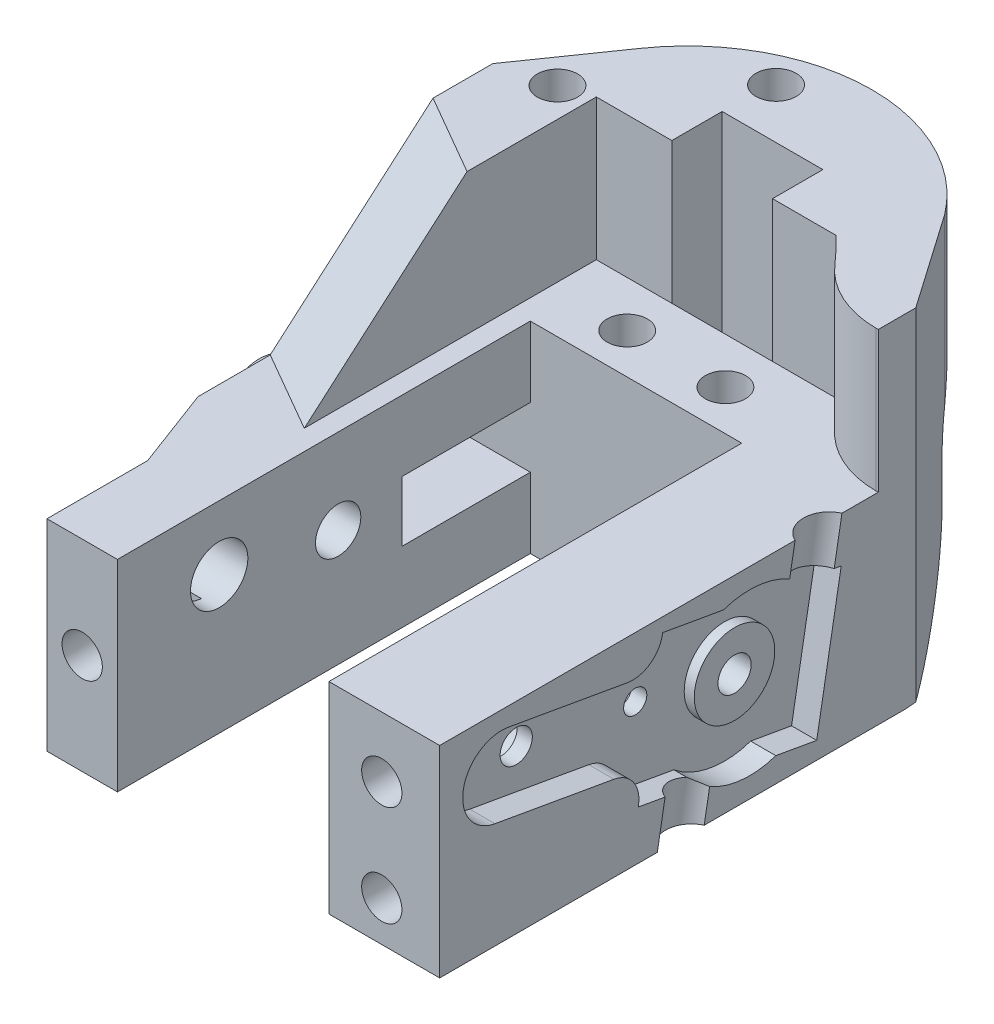
SolidWorks part; units mm, degrees
material "ABS"
ref_plane "Front Plane" through (0, 0, 0) normal (0, 0, 1) x (1, 0, 0)
ref_plane "Top Plane" through (0, 0, 0) normal (0, 1, 0) x (1, 0, 0)
ref_plane "Right Plane" through (0, 0, 0) normal (1, 0, 0) x (0, 0, -1)
sketch "Sketch1" plane through (0, 0, 0) normal (0, 1, 0) x (1, 0, 0)
  line L0 (-15.5, -37) -> (-10, -37)
  line L2 (-15.5, -37) -> (-15.5, 10)
  line L3 (-15.5, 10) -> (21, 10)
  line L4 (21, -19) -> (21, 10)
  line L5 (-10, -37) -> (-10, 4)
  line L6 (-10, 4) -> (11, 4)
  line L7 (11, 4) -> (11, -37)
  line L9 (21, -19) -> (18, -27)
  line L10 (18, -27) -> (18, -37)
  line L11 (11, -37) -> (18, -37)
  point P0 (0, 0)
  dimension "D1" = 36.5
  dimension "D2" = 7
  dimension "D3" = 21
  dimension "D4" = 10
  dimension "D5" = 21
  dimension "D6" = 41
  dimension "D7" = 47
  dimension "D8" = 8
  dimension "D9" = 5.5
  dimension "D10" = 10
extrude "Boss-Extrude1" add sketch "Sketch1" along normal blind 20
sketch "Sketch6" plane through (-15.5, 0, 0) normal (-1, 0, 0) x (0, 0, 1)
  line L1 (15, 0) -> (-10, 0)
  line L2 (15, 0) -> (15, 20)
  line L3 (15, 20) -> (-10, 20)
  line L4 (-10, 0) -> (-10, 20)
  line L5 (-10, 20) -> (-10, 0) construction
  line L7 (-10, 0) -> (37, 0) construction
  line L8 (-10, 20) -> (37, 20) construction
  dimension "D3" = 25
extrude "Boss-Extrude5" add sketch "Sketch6" along normal blind 5.5
sketch "Sketch20" plane through (0, 20, 0) normal (0, 1, 0) x (1, 0, 0)
  line L4 (-21, 6.5542) -> (13, 6.5542)
  line L11 (21.0063, -11.8234) -> (21.0063, 10.2821)
  line L12 (21.0063, 10.2821) -> (15.0032, 18.9016)
  line L13 (15.0032, 18.9016) -> (-14.9968, 18.9016)
  line L14 (-14.9968, 18.9016) -> (-21, 10.2821)
  line L15 (-21, 10) -> (-21, -15) construction
  line L16 (-21, 10.2821) -> (-21, 6.5542)
  line L18 (13, 6.5542) -> (13, -16.4458)
  line L20 (13, -16.4458) -> (21.0063, -11.8234)
  dimension "D2" = 23
  dimension "D4" = 30
  dimension "D8" = 34
  dimension "D9" = 60
  dimension "D1" = 6.0032
  dimension "D3" = 6.0032
  dimension "D5" = 8.6195
  dimension "D6" = 8.6195
  dimension "D7" = 3.7279
extrude "Boss-Extrude11" add sketch "Sketch20" along normal blind 14 and the other way up to surface (20 mm away) other way up to face at (0.5833, 0, 16.3333)
sketch "Sketch4" plane through (0, 20, 0) normal (0, 1, 0) x (1, 0, 0)
  line L2 (-10, 4) -> (11, 4) construction
  line L4 (-10, -37) -> (-10, 4) construction
  circle A6 centre (-4.375, 8) radius 2
  circle A7 centre (5.375, 8) radius 2
  dimension "D1" = 4
  dimension "D2" = 4
  dimension "D3" = 9.75
  dimension "D4" = 5.625
extrude "Cut-Extrude1" cut sketch "Sketch4" against normal blind 10
sketch "Sketch24" plane through (0, 34, 0) normal (0, 1, 0) x (1, 0, 0)
  line L0 (21.0063, 10.2821) -> (15.0032, 18.9016) construction
  line L1 (-14.9968, 18.9016) -> (-14.4209, 19.7285)
  line L2 (-21, 10.2821) -> (-21, 6.5542) construction
  line L3 (-14.9968, 18.9016) -> (-21, 10.2821) construction
  line L4 (21.0063, 10.2821) -> (15.0032, 18.9016)
  line L6 (-21, 10.2821) -> (-21, 6.5542)
  line L7 (-14.9968, 18.9016) -> (-21, 10.2821)
  line L11 (-21, 6.5542) -> (13, 6.5542) construction
  line L14 (-21, 6.5542) -> (21.0063, 6.5542)
  line L16 (21.0063, 10.2821) -> (21.0063, 6.5542)
  line L17 (21.0063, -11.8234) -> (21.0063, 10.2821) construction
  arc A3 (8.6131, 24.6437) -> (-14.4209, 19.7285) centre (-0.0555, 8.8374) ccw
  arc A4 (8.6131, 24.6437) -> (15.0032, 18.9016) centre (-0.4313, 8.152) cw
  dimension "D3" = 18.0273
  dimension "D4" = 18.8089
  dimension "D1" = 0.5759
  dimension "D2" = 1.0077
extrude "Boss-Extrude13" add sketch "Sketch24" against normal blind 12
fillet "Fillet11" radius 7.95 1 edges at (0.0032, 22, -18.9016)
chamfer "Chamfer1" distance 14 angle 45 1 edges at (17.0032, 34, 14.1346)
sketch "Sketch26" plane through (-21, 0, 0) normal (-1, 0, 0) x (0, 0, 1)
  line L0 (15, 0) -> (37, 0)
  line L2 (37, 0) -> (37, 20)
  line L3 (37, 20) -> (15, 20)
  line L4 (15, 0) -> (15, 20) construction
  line L5 (15, 20) -> (15, 0)
extrude "Boss-Extrude14" add sketch "Sketch26" against normal up to surface (11 mm away) up to face at (-10, 10, 16.5)
sketch "Sketch25" plane through (-21, 0, 0) normal (-1, 0, 0) x (0, 0, 1)
  line L0 (12.4376, 15.0315) -> (30.1652, 18.1573)
  line L1 (13.7834, 7.3992) -> (31.511, 10.5251)
  line L2 (31.511, 10.5251) -> (30.1652, 18.1573) construction
  line L3 (6.2179, 10) -> (30.8381, 14.3412) construction
  line L4 (-10.2821, 0) -> (37, 0) construction
  line L5 (6.2179, 10) -> (6.2179, 38.8588) construction
  line L7 (-10.2821, 34) -> (-10.2821, 0) construction
  arc A1 (12.4376, 15.0315) -> (13.7834, 7.3992) centre (6.2179, 10) ccw
  arc A3 (30.1652, 18.1573) -> (31.511, 10.5251) centre (30.8381, 14.3412) cw
  dimension "D1" = 8
  dimension "D2" = 7.75
  dimension "D4" = 7.75
  dimension "D3" = 25
  dimension "D5" = 80
  dimension "D7" = 10
  dimension "D6" = 16.5
extrude "Cut-Extrude7" cut sketch "Sketch25" against normal blind 2.5
sketch "Sketch27" plane through (-18.5, 0, 0) normal (-1, 0, 0) x (0, 0, 1)
  line L0 (6.2179, 10) -> (30.8381, 14.3412) construction
  circle A0 centre (6.2179, 10) radius 4
  circle A1 centre (15.0812, 11.5628) radius 1.15
  circle A4 centre (26.8989, 13.6466) radius 1.6
  dimension "D1" = 8
  dimension "D3" = 2.3
  dimension "D4" = 3.2
  dimension "D2" = 9
  dimension "D5" = 4
extrude "Cut-Extrude8" cut sketch "Sketch27" against normal up to next
sketch "Sketch28" plane through (-21, 0, 0) normal (-1, 0, 0) x (0, 0, 1)
  line L0 (-2.8761, 15.5045) -> (14.8505, 18.6301)
  line L1 (14.8505, 18.6301) -> (17.2815, 4.8428)
  line L2 (17.2815, 4.8428) -> (-0.445, 1.7172)
  line L3 (-0.445, 1.7172) -> (-2.8761, 15.5045)
  line L6 (30.1652, 18.1573) -> (12.4376, 15.0315) construction
  circle A0 centre (6.2179, 10) radius 4 construction
  dimension "D1" = 10
  dimension "D2" = 7
  dimension "D3" = 14
  dimension "D4" = 18
extrude "Cut-Extrude9" cut sketch "Sketch28" against normal blind 2.5
sketch "Sketch29" plane through (0, 15.5288, -2.7381) normal (0, -0.9848, 0.1736) x (1, 0, 0)
  line L0 (-18.5, 3.987) -> (-18.5, -0.14) construction
  line L3 (-21, 11.7329) -> (-21, 3.987) construction
  circle A0 centre (-22, 2.86) radius 2.5
  point P6 (-21, 7.86)
  dimension "D1" = 5
  dimension "D2" = 3.5
  dimension "D3" = 5
extrude "Cut-Extrude10" cut sketch "Sketch29" against normal up to next
sketch "Sketch30" plane through (0, 1.7415, -0.3071) normal (0, 0.9848, -0.1736) x (1, 0, 0)
  line L0 (-21, -11.7329) -> (-21, -17.86) construction
  line L1 (-21, -3.987) -> (-21, -11.7329) construction
  circle A0 centre (-22, -12.86) radius 2.5
  point P6 (-21, -7.86)
  dimension "D1" = 5
  dimension "D2" = 1
  dimension "D3" = 5
extrude "Cut-Extrude11" cut sketch "Sketch30" against normal up to next
sketch "Sketch31" plane through (-18.5, 0, 0) normal (-1, 0, 0) x (0, 0, 1)
  circle A0 centre (6.2179, 10) radius 4
  circle A1 centre (6.2179, 10) radius 1.65
  dimension "D1" = 8
  dimension "D2" = 3.3
extrude "Boss-Extrude15" add sketch "Sketch31" along normal blind 1 and the other way blind 2
sketch "Sketch32" plane through (-10, 0, 0) normal (1, 0, 0) x (0, 0, -1)
  circle A0 centre (-26.8989, 13.6466) radius 2.85
  circle A3 centre (-15.0812, 11.5628) radius 2.25
  dimension "D1" = 5.7
  dimension "D2" = 4.5
extrude "Cut-Extrude12" cut sketch "Sketch32" against normal blind 7 and the other way up to next
sketch "Sketch33" plane through (21.0063, 0, 0) normal (1, 0, 0) x (0, 0, -1)
  circle A0 centre (-6.2179, 10) radius 3.8
  circle A1 centre (-6.2179, 10) radius 1.65 construction
  dimension "D1" = 7.6
extrude "Boss-Extrude17" add sketch "Sketch33" along normal blind 7
fillet "Fillet17" radius 1 1 edges at (28.0063, 10, 2.4179)
sketch "Sketch35" plane through (0, 34, 0) normal (0, 1, 0) x (1, 0, 0)
  line L0 (-21, 6.5542) -> (13, 6.5542) construction
  line L1 (-20.8, 6.5542) -> (13, 6.5542)
  line L3 (-10.8027, 12.5542) -> (13, 12.5542)
  line L4 (13, 6.5542) -> (13, 12.5542)
  line L7 (13, 6.5542) -> (13, -0.28) construction
  arc A0 (-20.8, 6.5542) -> (-13.285, 9.9568) centre (-20.8, 16.5542) ccw
  arc A1 (-13.285, 9.9568) -> (-10.8027, 12.5542) centre (18.6614, -18.0889) cw
  dimension "D3" = 42.5104
  dimension "D4" = 10
  dimension "D5" = 8.2494
  dimension "D1" = 23.8027
  dimension "D2" = 6
  dimension "D6" = 9.9972
extrude "Cut-Extrude13" cut sketch "Sketch35" against normal up to surface (14 mm away) up to face at (1.4167, 20, 9.7117)
sketch "Sketch36" plane through (0, 0, 37) normal (0, 0, 1) x (1, 0, 0)
  line L0 (11, 20) -> (11, 0) construction
  line L1 (11, 20) -> (18, 20) construction
  line L2 (-21, 0) -> (-21, 20) construction
  line L6 (-21, 20) -> (-10, 20) construction
  circle A0 centre (-15.25, 14) radius 2
  circle A1 centre (14.5, 10) radius 2
  circle A2 centre (-15.25, 4) radius 2
  dimension "D3" = 4
  dimension "D1" = 5.75
  dimension "D2" = 3.5
  dimension "D4" = 10
  dimension "D5" = 6
  dimension "D6" = 5.75
  dimension "D7" = 10
extrude "Cut-Extrude14" cut sketch "Sketch36" against normal blind 10
fillet "Fillet18" radius 10 1 edges at (0.0032, 0, -18.9016)
sketch "Sketch37" plane through (21, 0, 0) normal (1, 0, 0) x (0, 0, -1)
  line L0 (-6.2179, 10) -> (6.304, 10) construction
  line L1 (4, 20) -> (4, 0) construction
  line L2 (-1.7179, 13) -> (4, 13)
  line L3 (-1.7179, 13) -> (-1.7179, 7)
  line L4 (-1.7179, 7) -> (4, 7)
  line L5 (4, 13) -> (4, 7)
  point P7 (0.043, 10)
  dimension "D1" = 6
  dimension "D2" = 3
  dimension "D4" = 4.5
extrude "Cut-Extrude16" cut sketch "Sketch37" against normal up to next
chamfer "Chamfer2" distance 7 angle 45 1 edges at (11, 10, 1.7179)
sketch "Sketch38" plane through (0, 0, 0) normal (0, -1, 0) x (1, 0, 0)
  line L0 (-10, -4) -> (11, -4) construction
  line L1 (-4.5, -4) -> (5.5, -4)
  line L2 (-4.5, -4) -> (-4.5, -24)
  line L3 (-4.5, -24) -> (5.5, -24)
  line L4 (5.5, -4) -> (5.5, -24)
  line L5 (-10, 37) -> (-10, -4) construction
  dimension "D1" = 10
  dimension "D2" = 5.5
  dimension "D3" = 20
extrude "Cut-Extrude17" cut sketch "Sketch38" against normal blind 4
sketch "Sketch39" plane through (0, 34, 0) normal (0, 1, 0) x (1, 0, 0)
  line L0 (13, 12.5542) -> (-10.8027, 12.5542) construction
  line L1 (-4.5, 12.5542) -> (5.5, 12.5542)
  line L2 (-4.5, 12.5542) -> (-4.5, 17.5542)
  line L3 (-4.5, 17.5542) -> (5.5, 17.5542)
  line L4 (5.5, 12.5542) -> (5.5, 17.5542)
  line L5 (5.5, 16.9016) -> (5.5, 4) construction
  line L6 (-4.5, 4) -> (-4.5, 16.9016) construction
  dimension "D1" = 5
extrude "Cut-Extrude19" cut sketch "Sketch39" against normal up to next
ref_plane "Plane1" through (-31, 0, 0) normal (-1, 0, 0) x (0, 0, 1)
mirror "Mirror1" about plane through (-31, 0, 0) normal (-1, 0, 0) of bodies 140
sketch "Sketch40" plane through (0, 0, -18.9016) normal (0, 0, -1) x (-1, 0, 0)
  line L1 (-37.1576, -4.2201) -> (26.4203, -4.2201)
  line L2 (-37.1576, -4.2201) -> (-37.1576, 81.1631)
  line L3 (-37.1576, 81.1631) -> (26.4203, 81.1631)
  line L4 (26.4203, -4.2201) -> (26.4203, 81.1631)
extrude "Cut-Extrude20" cut sketch "Sketch40" against normal through all both and the other way through all
sketch "Sketch41" plane through (0, 34, 0) normal (0, 1, 0) x (1, 0, 0)
  circle A0 centre (-67.1107, 22.5147) radius 2
  circle A1 centre (-77.9107, 11.6065) radius 2
  dimension "D1" = 4
  dimension "D2" = 10.8
  dimension "D3" = 10.9081
  dimension "D4" = 5.0956
  dimension "D5" = 1.3245
extrude "Cut-Extrude21" cut sketch "Sketch41" against normal blind 8
fillet "Fillet19" radius 3 2 edges at (-42.25, 7.9204, 16.7389) (-42.25, 15.5526, 15.3931)
equation "\"D4@Sketch4\"=(21-\"D3@Sketch4\")/2"
equation "\"D2@Sketch37\"=\"D1@Sketch37\"/2"
equation "\"D3@Sketch20\"=\"D1@Sketch20\""
equation "\"D6@Sketch20\"=\"D5@Sketch20\""
equation "\"D2@Sketch25\"=\"D4@Sketch25\""
